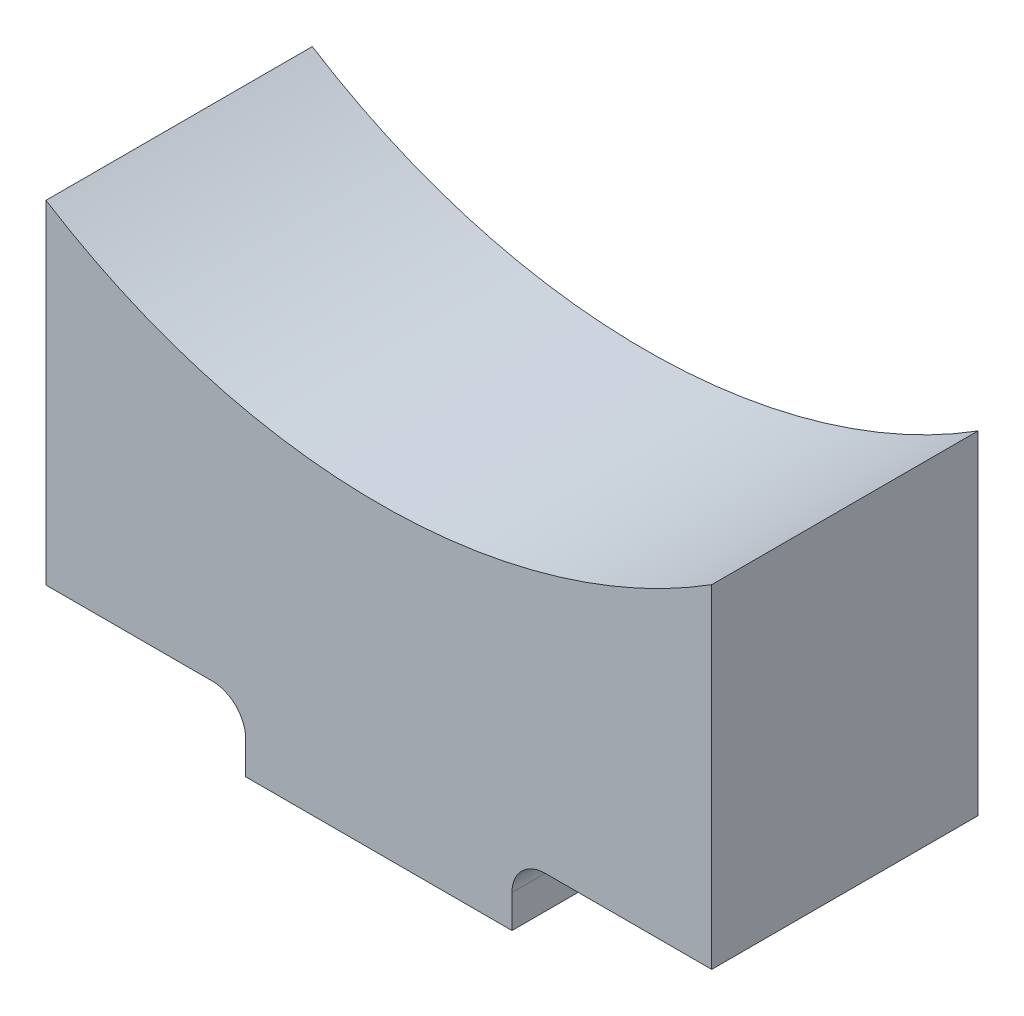
SolidWorks part; units mm, degrees
material "Ice"
ref_plane "Front Plane" through (0, 0, 0) normal (0, 0, 1) x (1, 0, 0)
ref_plane "Top Plane" through (0, 0, 0) normal (0, 1, 0) x (1, 0, 0)
ref_plane "Right Plane" through (0, 0, 0) normal (1, 0, 0) x (0, 0, -1)
sketch "Sketch1" plane through (0, 0, 0) normal (0, 0, 1) x (1, 0, 0)
  line L0 (10, 3.9928) -> (10, -6.0185)
  line L1 (-10, 3.9928) -> (-10, -6.0185)
  line L2 (-10, -6.0185) -> (-5, -6.0185)
  line L3 (10, -6.0185) -> (5, -6.0185)
  line L4 (4, -7.0185) -> (4, -8.0072)
  line L5 (0, 0) -> (0, 15264.4079) construction
  line L6 (-4, -7.0185) -> (-4, -8.0072)
  line L11 (-4, -8.0072) -> (4, -8.0072)
  arc A0 (-10, 3.9928) -> (10, 3.9928) centre (0, 19.8337) ccw
  arc A1 (4, -7.0185) -> (5, -6.0185) centre (5, -7.0185) cw
  arc A2 (-4, -7.0185) -> (-5, -6.0185) centre (-5, -7.0185) ccw
  point P13 (4, -6.0185)
  dimension "D1" = 10
  dimension "D2" = 10
  dimension "D3" = 12
extrude "Boss-Extrude1" add sketch "Sketch1" along normal mid plane 8 contours A0 L0 L3 A1 L4 L11 L6 A2 L2 L1
